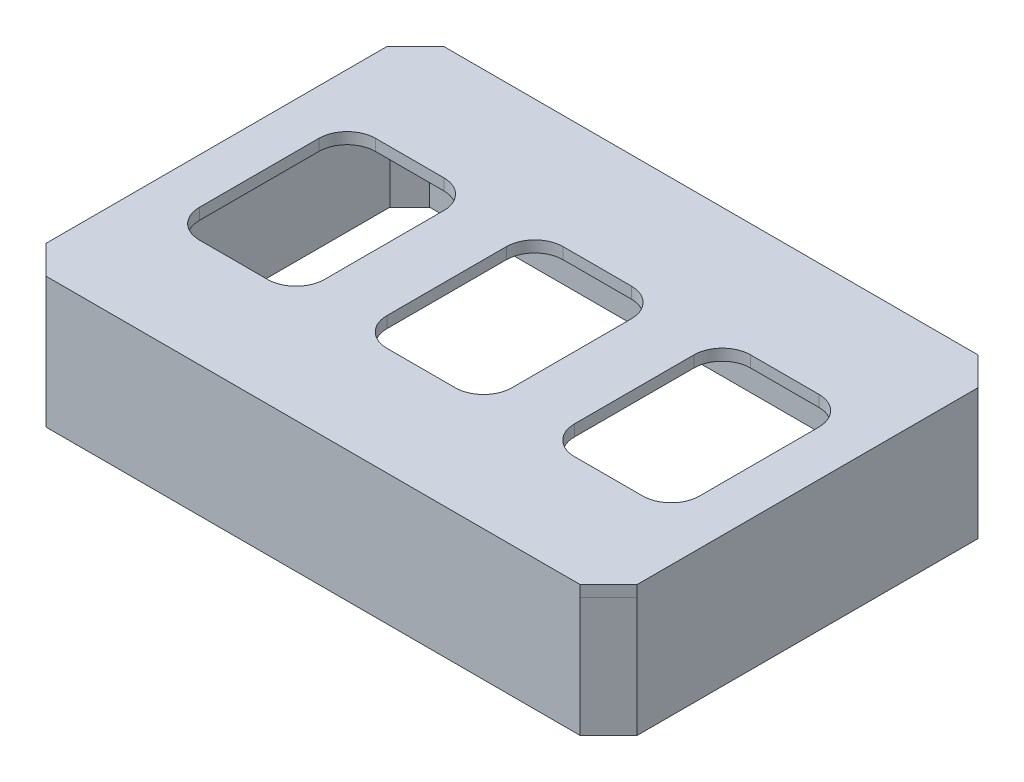
SolidWorks part; units mm, degrees
ref_plane "Front Plane" through (0, 0, 0) normal (0, 0, 1) x (1, 0, 0)
ref_plane "Top Plane" through (0, 0, 0) normal (0, 1, 0) x (1, 0, 0)
ref_plane "Right Plane" through (0, 0, 0) normal (1, 0, 0) x (0, 0, -1)
sketch "Sketch1" plane through (0, 0, 0) normal (0, 1, 0) x (1, 0, 0)
  line L1 (-50.25, -32.25) -> (50.25, -32.25)
  line L2 (-50.25, -32.25) -> (-50.25, 32.25)
  line L3 (-50.25, 32.25) -> (50.25, 32.25)
  line L4 (50.25, -32.25) -> (50.25, 32.25)
  line L5 (-50.25, -32.25) -> (50.25, 32.25) construction
  line L6 (-50.25, 32.25) -> (50.25, -32.25) construction
  line L7 (-52, -35) -> (52, -35)
  line L8 (-52, -35) -> (-52, 35)
  line L9 (-52, 35) -> (52, 35)
  line L10 (52, -35) -> (52, 35)
  line L11 (-52, -35) -> (52, 35) construction
  line L12 (-52, 35) -> (52, -35) construction
  point P0 (0, 0)
  point P6 (0, 0)
  dimension "D1" = 100.5
  dimension "D2" = 64.5
  dimension "D3" = 2.75
  dimension "D4" = 1.75
extrude "Boss-Extrude1" add sketch "Sketch1" along normal blind 21
chamfer "Chamfer2" distance 3.5 angle 45 4 edges at (50.25, 10.5, 32.25) (-50.25, 10.5, 32.25) (-50.25, 10.5, -32.25) (50.25, 10.5, -32.25)
chamfer "Chamfer3" distance 5 angle 45 4 edges at (-52, 10.5, 35) (52, 10.5, 35) (52, 10.5, -35) (-52, 10.5, -35)
sketch "Sketch3" plane through (0, 21, 0) normal (0, 1, 0) x (1, 0, 0)
  line L1 (-52, 35) -> (52, 35)
  line L2 (-52, 35) -> (-52, -35)
  line L3 (-52, -35) -> (52, -35)
  line L4 (52, 35) -> (52, -35)
extrude "Boss-Extrude2" add sketch "Sketch3" along normal blind 2
chamfer "Chamfer4" distance 5 angle 45 4 edges at (-52, 22, 35) (52, 22, 35) (52, 22, -35) (-52, 22, -35)
sketch "Sketch4" plane through (0, 21, 0) normal (0, -1, 0) x (1, 0, 0)
  line L0 (-50.25, -28.75) -> (-50.25, 28.75) construction
  line L1 (-11, 16) -> (11, 16)
  line L2 (-11, 16) -> (-11, -15)
  line L3 (-11, -15) -> (11, -15)
  line L4 (11, 16) -> (11, -15)
  line L5 (22, 16) -> (44, 16)
  line L6 (22, 16) -> (22, -15)
  line L7 (22, -15) -> (44, -15)
  line L8 (44, 16) -> (44, -15)
  line L9 (-22, 16) -> (-44, 16)
  line L10 (-22, 16) -> (-22, -15)
  line L11 (-22, -15) -> (-44, -15)
  line L12 (-44, 16) -> (-44, -15)
  line L15 (46.75, -32.25) -> (-46.75, -32.25) construction
  dimension "D1" = 22
  dimension "D2" = 22
  dimension "D3" = 22
  dimension "D4" = 31
  dimension "D5" = 31
  dimension "D6" = 31
  dimension "D7" = 11
  dimension "D8" = 11
  dimension "D9" = 6.25
  dimension "D10" = 17.25
extrude "Cut-Extrude1" cut sketch "Sketch4" against normal blind 2
fillet "Fillet1" radius 5 12 edges at (22, 22, 16) (-11, 22, 16) (-44, 22, 16) (-22, 22, 16) (11, 22, 16) (44, 22, 16) (22, 22, -15) (-11, 22, -15) (44, 22, -15) (11, 22, -15) (-22, 22, -15) (-44, 22, -15)
